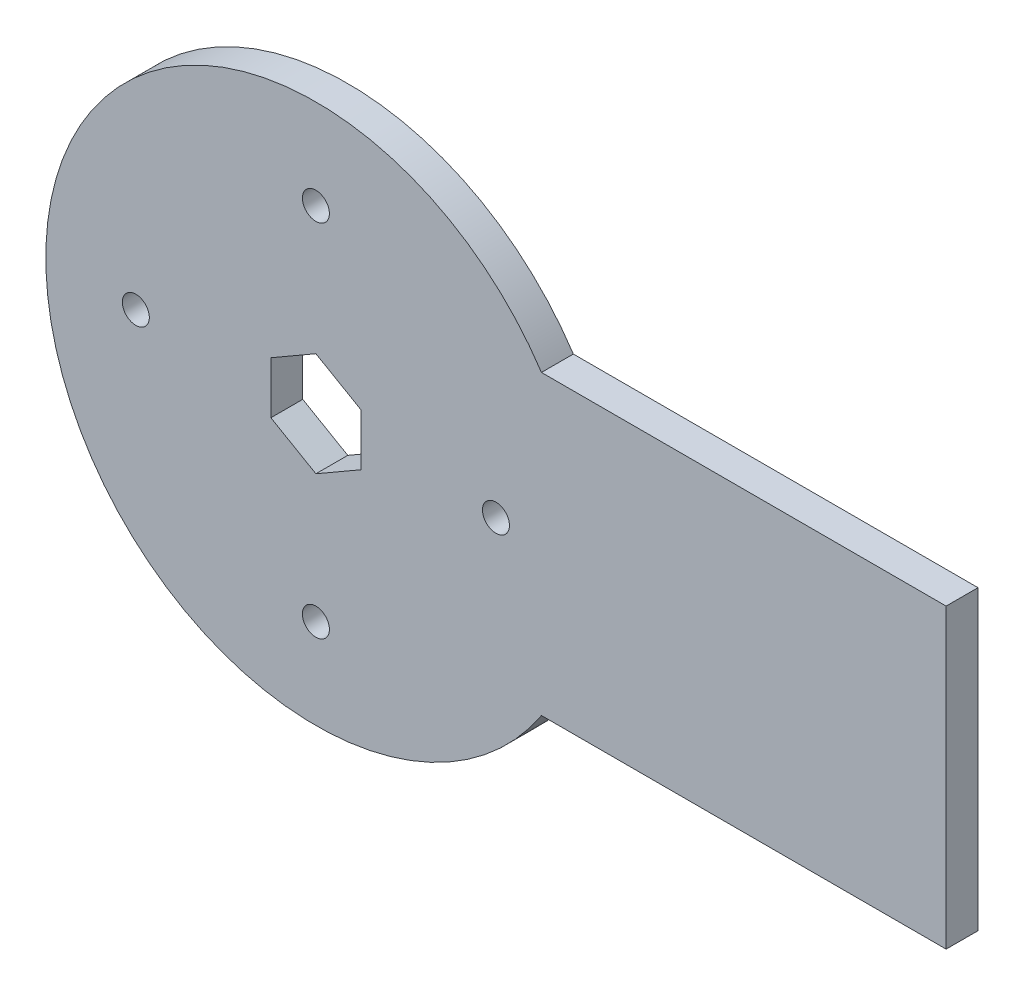
SolidWorks part; units mm, degrees
ref_plane "前视基准面" through (0, 0, 0) normal (0, 0, 1) x (1, 0, 0)
ref_plane "上视基准面" through (0, 0, 0) normal (0, 1, 0) x (1, 0, 0)
ref_plane "右视基准面" through (0, 0, 0) normal (1, 0, 0) x (0, 0, -1)
sketch "Sketch1" plane through (0, 0, 0) normal (0, 0, 1) x (1, 0, 0)
  circle A0 centre (0, 0) radius 30
extrude "Boss-Extrude1" add sketch "Sketch1" along normal blind 3.54
sketch "Sketch3" plane through (0, 0, 3.54) normal (0, 0, 1) x (1, 0, 0)
  circle A1 centre (12, 5) radius 4
  dimension "D1" = 5
  dimension "D2" = 12
sketch "Sketch4" plane through (0, 0, 3.54) normal (0, 0, 1) x (1, 0, 0)
  line L0 (25.7688, 0) -> (75.3766, 0) construction
  line L1 (25.0549, 16.5) -> (70, 16.5)
  line L2 (25.0549, -16.5) -> (70, -16.5)
  line L3 (30, 0) -> (30, 16.5) construction
  line L4 (70, 16.5) -> (70, -16.5)
  circle A0 centre (0, 0) radius 30 construction
  arc A1 (25.0549, 16.5) -> (25.0549, -16.5) centre (0, 0) cw
  dimension "D1" = 16.5
  dimension "D2" = 40
extrude "Boss-Extrude4" add sketch "Sketch4" against normal blind 3.54
sketch "Sketch9" plane through (0, 0, 0) normal (0, 0, -1) x (-1, 0, 0)
  line L1 (0, 5.7735) -> (-5, 2.8868)
  line L2 (-5, 2.8868) -> (-5, -2.8868)
  line L3 (-5, -2.8868) -> (0, -5.7735)
  line L4 (0, -5.7735) -> (5, -2.8868)
  line L5 (5, -2.8868) -> (5, 2.8868)
  line L6 (5, 2.8868) -> (0, 5.7735)
  circle A0 centre (0, 0) radius 5 construction
extrude "Cut-Extrude3" cut sketch "Sketch9" against normal blind 6
sketch "Sketch10" plane through (0, 0, 3.54) normal (0, 0, 1) x (1, 0, 0)
  circle A0 centre (0, 0) radius 20 construction
  circle A1 centre (0, 20) radius 1.5
  circle A2 centre (20, 0) radius 1.5
  circle A3 centre (0, -20) radius 1.5
  circle A4 centre (-20, 0) radius 1.5
  dimension "D1" = 4
extrude "Cut-Extrude4" cut sketch "Sketch10" against normal blind 10
